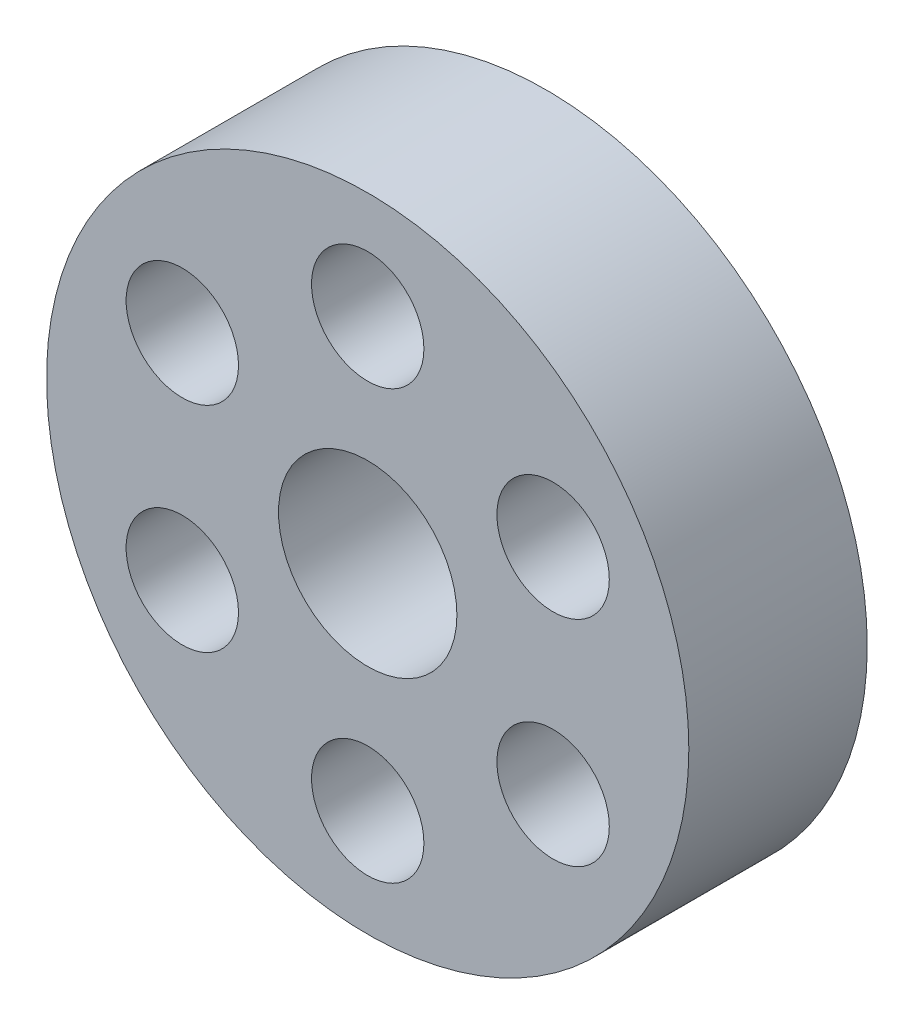
SolidWorks part; units mm, degrees
ref_plane "Front Plane" through (0, 0, 0) normal (0, 0, 1) x (1, 0, 0)
ref_plane "Top Plane" through (0, 0, 0) normal (0, 1, 0) x (1, 0, 0)
ref_plane "Right Plane" through (0, 0, 0) normal (1, 0, 0) x (0, 0, -1)
sketch "Sketch1" plane through (0, 0, 0) normal (0, 0, 1) x (1, 0, 0)
  circle A0 centre (0, 0) radius 11.43
  circle A1 centre (0, 0) radius 3.175
extrude "Boss-Extrude1" add sketch "Sketch1" along normal blind 6.35
sketch "Sketch4" plane through (0, 0, 6.35) normal (0, 0, 1) x (1, 0, 0)
  line L0 (0, -55) -> (0, 55) construction
  point P0 (0, 7.62)
hole_wizard "Ø4.0mm Dowel Hole2" positions "Sketch4" profile "Sketch5" hole size "Ø4.0" standard "ANSI Metric" end condition through all
sketch "Sketch5" plane through (0, 7.62, 6.35) normal (1, 0, 0) x (0, -1, 0)
  line L0 (0, 0) -> (0, 6.35)
  line L1 (0, 6.35) -> (2, 6.35)
  line L2 (2, 6.35) -> (2, 0)
  line L5 (2, 0) -> (0, 0)
  line L11 (0, -6.35) -> (0, 107.95) construction
  dimension "Thru Hole Dia." = 4
  dimension "Thru Hole Depth" = 6.35
pattern_circular "CirPattern1" count 6 over 360 about axis through (0, 0, 6.35) along (0, 0, -1) of "Ø4.0mm Dowel Hole2" reverse direction yes
